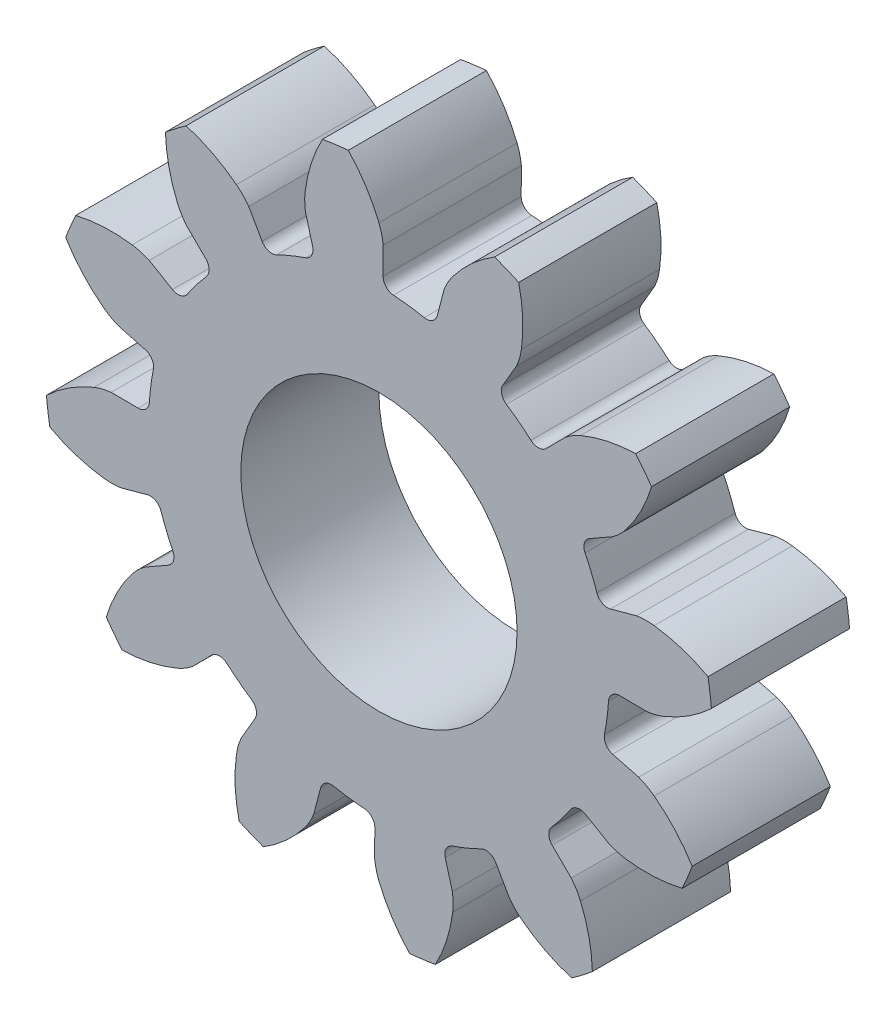
SolidWorks part; units mm, degrees
ref_plane "Front Plane" through (0, 0, 0) normal (0, 0, 1) x (1, 0, 0)
ref_plane "Top Plane" through (0, 0, 0) normal (0, 1, 0) x (1, 0, 0)
ref_plane "Right Plane" through (0, 0, 0) normal (1, 0, 0) x (0, 0, -1)
sketch "Sketch1" plane through (0, 0, 0) normal (0, 0, 1) x (1, 0, 0)
  line L48 (-1.0632, 3.7284) -> (-0.9599, 3.3519)
  line L49 (-1.6914, 3.0489) -> (-1.8846, 3.3881)
  line L50 (-2.7849, 2.6973) -> (-2.5072, 2.4228)
  line L51 (-2.9892, 1.7947) -> (-3.3262, 1.9919)
  line L52 (-3.7605, 0.9435) -> (-3.3827, 0.8446)
  line L53 (-3.4861, 0.0597) -> (-3.8765, 0.0619)
  line L54 (-3.7284, -1.0632) -> (-3.3519, -0.9599)
  line L55 (-3.0489, -1.6914) -> (-3.3881, -1.8846)
  line L56 (-2.6973, -2.7849) -> (-2.4228, -2.5072)
  line L57 (-1.7947, -2.9892) -> (-1.9919, -3.3262)
  line L58 (-0.9435, -3.7605) -> (-0.8446, -3.3827)
  line L59 (-0.0597, -3.4861) -> (-0.0619, -3.8765)
  line L60 (1.0632, -3.7284) -> (0.9599, -3.3519)
  line L61 (1.6914, -3.0489) -> (1.8846, -3.3881)
  line L62 (2.7849, -2.6973) -> (2.5072, -2.4228)
  line L63 (2.9892, -1.7947) -> (3.3262, -1.9919)
  line L64 (3.7605, -0.9435) -> (3.3827, -0.8446)
  line L65 (3.4861, -0.0597) -> (3.8765, -0.0619)
  line L66 (3.7284, 1.0632) -> (3.3519, 0.9599)
  line L67 (3.0489, 1.6914) -> (3.3881, 1.8846)
  line L68 (2.6973, 2.7849) -> (2.4228, 2.5072)
  line L69 (1.7947, 2.9892) -> (1.9919, 3.3262)
  line L70 (0.9435, 3.7605) -> (0.8446, 3.3827)
  line L71 (0.0597, 3.4861) -> (0.0619, 3.8765)
  circle A0 centre (0, 0) radius 2
  arc A192 (0.0001, 4.1255) -> (-0.4435, 4.8135) centre (-2.0446, 3.2941) ccw
  arc A193 (-0.4435, 4.8135) -> (-0.8175, 4.7642) centre (0, 0) ccw
  arc A194 (-0.8175, 4.7642) -> (-1.0679, 3.9849) centre (1.1224, 3.711) ccw
  arc A195 (-1.0679, 3.9849) -> (-1.0632, 3.7284) centre (-0.174, 3.8731) ccw
  arc A196 (-1.0643, 3.1556) -> (-0.9599, 3.3519) centre (-1.1161, 3.309) ccw
  arc A197 (-1.0643, 3.1556) -> (-1.4787, 2.9839) centre (0, 0) ccw
  arc A198 (-1.6914, 3.0489) -> (-1.4787, 2.9839) centre (-1.5507, 3.129) ccw
  arc A199 (-1.8846, 3.3881) -> (-2.0626, 3.5729) centre (-2.6156, 2.8618) ccw
  arc A200 (-2.0626, 3.5729) -> (-2.7908, 3.9469) centre (-3.4177, 1.8304) ccw
  arc A201 (-2.7908, 3.9469) -> (-3.0901, 3.7172) centre (0, 0) ccw
  arc A202 (-3.0901, 3.7172) -> (-2.9173, 2.9171) centre (-0.8835, 3.775) ccw
  arc A203 (-2.9173, 2.9171) -> (-2.7849, 2.6973) centre (-2.0873, 3.2672) ccw
  arc A204 (-2.4995, 2.2007) -> (-2.5072, 2.4228) centre (-2.6211, 2.3077) ccw
  arc A205 (-2.4995, 2.2007) -> (-2.7726, 1.8448) centre (0, 0) ccw
  arc A206 (-2.9892, 1.7947) -> (-2.7726, 1.8448) centre (-2.9074, 1.9345) ccw
  arc A207 (-3.3262, 1.9919) -> (-3.5727, 2.0629) centre (-3.6961, 1.1706) ccw
  arc A208 (-3.5727, 2.0629) -> (-4.3903, 2.0227) centre (-3.875, -0.1237) ccw
  arc A209 (-4.3903, 2.0227) -> (-4.5347, 1.6742) centre (0, 0) ccw
  arc A210 (-4.5347, 1.6742) -> (-3.985, 1.0676) centre (-2.6526, 2.8275) ccw
  arc A211 (-3.985, 1.0676) -> (-3.7605, 0.9435) centre (-3.4412, 1.7858) ccw
  arc A212 (-3.265, 0.6561) -> (-3.3827, 0.8446) centre (-3.4237, 0.688) ccw
  arc A213 (-3.265, 0.6561) -> (-3.3235, 0.2113) centre (0, 0) ccw
  arc A214 (-3.4861, 0.0597) -> (-3.3235, 0.2113) centre (-3.4851, 0.2216) ccw
  arc A215 (-3.8765, 0.0619) -> (-4.1255, 0.0001) centre (-3.7862, -0.8343) ccw
  arc A216 (-4.1255, 0.0001) -> (-4.8135, -0.4435) centre (-3.2941, -2.0446) ccw
  arc A217 (-4.8135, -0.4435) -> (-4.7642, -0.8175) centre (0, 0) ccw
  arc A218 (-4.7642, -0.8175) -> (-3.9849, -1.0679) centre (-3.711, 1.1224) ccw
  arc A219 (-3.9849, -1.0679) -> (-3.7284, -1.0632) centre (-3.8731, -0.174) ccw
  arc A220 (-3.1556, -1.0643) -> (-3.3519, -0.9599) centre (-3.309, -1.1161) ccw
  arc A221 (-3.1556, -1.0643) -> (-2.9839, -1.4787) centre (0, 0) ccw
  arc A222 (-3.0489, -1.6914) -> (-2.9839, -1.4787) centre (-3.129, -1.5507) ccw
  arc A223 (-3.3881, -1.8846) -> (-3.5729, -2.0626) centre (-2.8618, -2.6156) ccw
  arc A224 (-3.5729, -2.0626) -> (-3.9469, -2.7908) centre (-1.8304, -3.4177) ccw
  arc A225 (-3.9469, -2.7908) -> (-3.7172, -3.0901) centre (0, 0) ccw
  arc A226 (-3.7172, -3.0901) -> (-2.9171, -2.9173) centre (-3.775, -0.8835) ccw
  arc A227 (-2.9171, -2.9173) -> (-2.6973, -2.7849) centre (-3.2672, -2.0873) ccw
  arc A228 (-2.2007, -2.4995) -> (-2.4228, -2.5072) centre (-2.3077, -2.6211) ccw
  arc A229 (-2.2007, -2.4995) -> (-1.8448, -2.7726) centre (0, 0) ccw
  arc A230 (-1.7947, -2.9892) -> (-1.8448, -2.7726) centre (-1.9345, -2.9074) ccw
  arc A231 (-1.9919, -3.3262) -> (-2.0629, -3.5727) centre (-1.1706, -3.6961) ccw
  arc A232 (-2.0629, -3.5727) -> (-2.0227, -4.3903) centre (0.1237, -3.875) ccw
  arc A233 (-2.0227, -4.3903) -> (-1.6742, -4.5347) centre (0, 0) ccw
  arc A234 (-1.6742, -4.5347) -> (-1.0676, -3.985) centre (-2.8275, -2.6526) ccw
  arc A235 (-1.0676, -3.985) -> (-0.9435, -3.7605) centre (-1.7858, -3.4412) ccw
  arc A236 (-0.6561, -3.265) -> (-0.8446, -3.3827) centre (-0.688, -3.4237) ccw
  arc A237 (-0.6561, -3.265) -> (-0.2113, -3.3235) centre (0, 0) ccw
  arc A238 (-0.0597, -3.4861) -> (-0.2113, -3.3235) centre (-0.2216, -3.4851) ccw
  arc A239 (-0.0619, -3.8765) -> (-0.0001, -4.1255) centre (0.8343, -3.7862) ccw
  arc A240 (-0.0001, -4.1255) -> (0.4435, -4.8135) centre (2.0446, -3.2941) ccw
  arc A241 (0.4435, -4.8135) -> (0.8175, -4.7642) centre (0, 0) ccw
  arc A242 (0.8175, -4.7642) -> (1.0679, -3.9849) centre (-1.1224, -3.711) ccw
  arc A243 (1.0679, -3.9849) -> (1.0632, -3.7284) centre (0.174, -3.8731) ccw
  arc A244 (1.0643, -3.1556) -> (0.9599, -3.3519) centre (1.1161, -3.309) ccw
  arc A245 (1.0643, -3.1556) -> (1.4787, -2.9839) centre (0, 0) ccw
  arc A246 (1.6914, -3.0489) -> (1.4787, -2.9839) centre (1.5507, -3.129) ccw
  arc A247 (1.8846, -3.3881) -> (2.0626, -3.5729) centre (2.6156, -2.8618) ccw
  arc A248 (2.0626, -3.5729) -> (2.7908, -3.9469) centre (3.4177, -1.8304) ccw
  arc A249 (2.7908, -3.9469) -> (3.0901, -3.7172) centre (0, 0) ccw
  arc A250 (3.0901, -3.7172) -> (2.9173, -2.9171) centre (0.8835, -3.775) ccw
  arc A251 (2.9173, -2.9171) -> (2.7849, -2.6973) centre (2.0873, -3.2672) ccw
  arc A252 (2.4995, -2.2007) -> (2.5072, -2.4228) centre (2.6211, -2.3077) ccw
  arc A253 (2.4995, -2.2007) -> (2.7726, -1.8448) centre (0, 0) ccw
  arc A254 (2.9892, -1.7947) -> (2.7726, -1.8448) centre (2.9074, -1.9345) ccw
  arc A255 (3.3262, -1.9919) -> (3.5727, -2.0629) centre (3.6961, -1.1706) ccw
  arc A256 (3.5727, -2.0629) -> (4.3903, -2.0227) centre (3.875, 0.1237) ccw
  arc A257 (4.3903, -2.0227) -> (4.5347, -1.6742) centre (0, 0) ccw
  arc A258 (4.5347, -1.6742) -> (3.985, -1.0676) centre (2.6526, -2.8275) ccw
  arc A259 (3.985, -1.0676) -> (3.7605, -0.9435) centre (3.4412, -1.7858) ccw
  arc A260 (3.265, -0.6561) -> (3.3827, -0.8446) centre (3.4237, -0.688) ccw
  arc A261 (3.265, -0.6561) -> (3.3235, -0.2113) centre (0, 0) ccw
  arc A262 (3.4861, -0.0597) -> (3.3235, -0.2113) centre (3.4851, -0.2216) ccw
  arc A263 (3.8765, -0.0619) -> (4.1255, -0.0001) centre (3.7862, 0.8343) ccw
  arc A264 (4.1255, -0.0001) -> (4.8135, 0.4435) centre (3.2941, 2.0446) ccw
  arc A265 (4.8135, 0.4435) -> (4.7642, 0.8175) centre (0, 0) ccw
  arc A266 (4.7642, 0.8175) -> (3.9849, 1.0679) centre (3.711, -1.1224) ccw
  arc A267 (3.9849, 1.0679) -> (3.7284, 1.0632) centre (3.8731, 0.174) ccw
  arc A268 (3.1556, 1.0643) -> (3.3519, 0.9599) centre (3.309, 1.1161) ccw
  arc A269 (3.1556, 1.0643) -> (2.9839, 1.4787) centre (0, 0) ccw
  arc A270 (3.0489, 1.6914) -> (2.9839, 1.4787) centre (3.129, 1.5507) ccw
  arc A271 (3.3881, 1.8846) -> (3.5729, 2.0626) centre (2.8618, 2.6156) ccw
  arc A272 (3.5729, 2.0626) -> (3.9469, 2.7908) centre (1.8304, 3.4177) ccw
  arc A273 (3.9469, 2.7908) -> (3.7172, 3.0901) centre (0, 0) ccw
  arc A274 (3.7172, 3.0901) -> (2.9171, 2.9173) centre (3.775, 0.8835) ccw
  arc A275 (2.9171, 2.9173) -> (2.6973, 2.7849) centre (3.2672, 2.0873) ccw
  arc A276 (2.2007, 2.4995) -> (2.4228, 2.5072) centre (2.3077, 2.6211) ccw
  arc A277 (2.2007, 2.4995) -> (1.8448, 2.7726) centre (0, 0) ccw
  arc A278 (1.7947, 2.9892) -> (1.8448, 2.7726) centre (1.9345, 2.9074) ccw
  arc A279 (1.9919, 3.3262) -> (2.0629, 3.5727) centre (1.1706, 3.6961) ccw
  arc A280 (2.0629, 3.5727) -> (2.0227, 4.3903) centre (-0.1237, 3.875) ccw
  arc A281 (2.0227, 4.3903) -> (1.6742, 4.5347) centre (0, 0) ccw
  arc A282 (1.6742, 4.5347) -> (1.0676, 3.985) centre (2.8275, 2.6526) ccw
  arc A283 (1.0676, 3.985) -> (0.9435, 3.7605) centre (1.7858, 3.4412) ccw
  arc A284 (0.6561, 3.265) -> (0.8446, 3.3827) centre (0.688, 3.4237) ccw
  arc A285 (0.6561, 3.265) -> (0.2113, 3.3235) centre (0, 0) ccw
  arc A286 (0.0597, 3.4861) -> (0.2113, 3.3235) centre (0.2216, 3.4851) ccw
  arc A287 (0.0619, 3.8765) -> (0.0001, 4.1255) centre (-0.8343, 3.7862) ccw
  dimension "D1" = 4
extrude "Boss-Extrude1" add sketch "Sketch1" along normal blind 2
